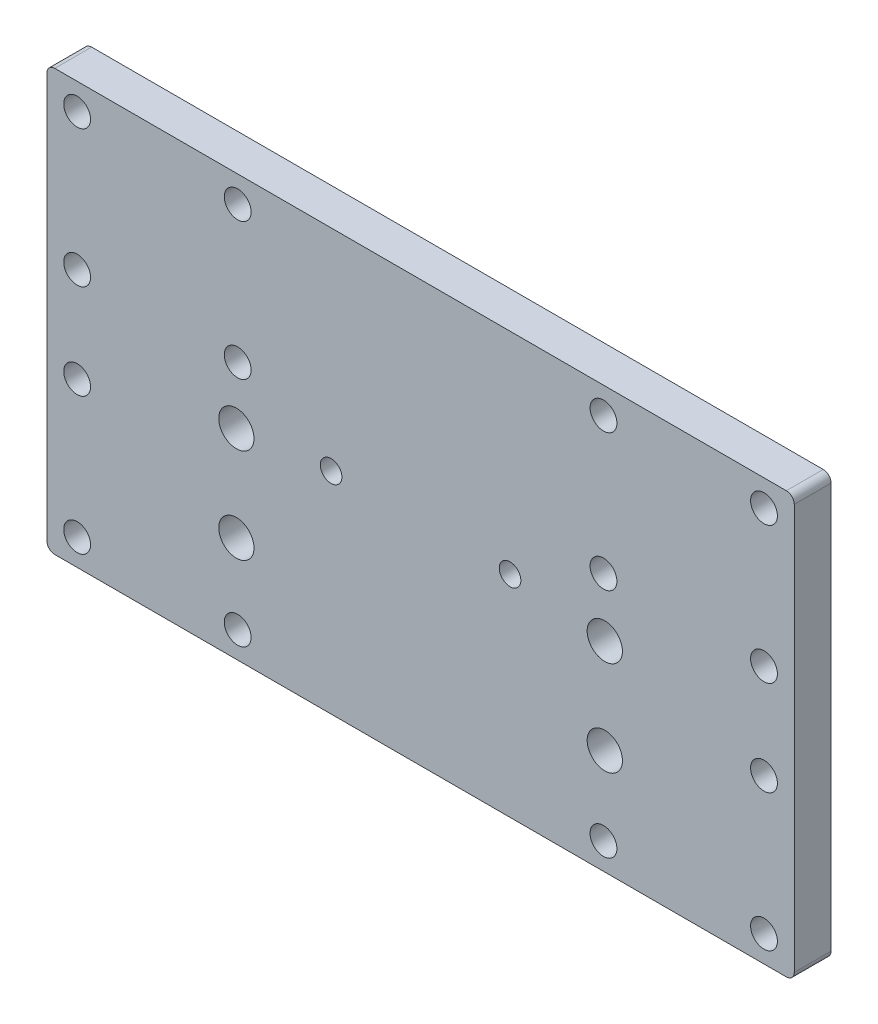
SolidWorks part; units mm, degrees
ref_plane "Front Plane" through (0, 0, 0) normal (0, 0, 1) x (1, 0, 0)
ref_plane "Top Plane" through (0, 0, 0) normal (0, 1, 0) x (1, 0, 0)
ref_plane "Right Plane" through (0, 0, 0) normal (1, 0, 0) x (0, 0, -1)
sketch "Sketch1" plane through (0, 0, 0) normal (0, 0, 1) x (1, 0, 0)
  line L1 (-71, -40) -> (71, -40)
  line L2 (-71, -40) -> (-71, 40)
  line L3 (-71, 40) -> (71, 40)
  line L4 (71, -40) -> (71, 40)
  line L5 (-71, -40) -> (71, 40) construction
  line L6 (-71, 40) -> (71, -40) construction
  point P0 (0, 0)
  dimension "D1" = 80
  dimension "D2" = 142
extrude "Boss-Extrude1" add sketch "Sketch1" along normal mid plane 7
sketch "Sketch2" plane through (0, 0, 3.5) normal (0, 0, 1) x (1, 0, 0)
  line L3 (-65.25, 40) -> (-65.25, -40)
  line L4 (-65.25, 40) -> (-65.25, -40) construction
  line L6 (65.25, -40) -> (65.25, 40)
  line L7 (65.25, -40) -> (65.25, 40) construction
  line L13 (-34.75, 40) -> (-34.75, -40)
  line L14 (-34.75, 40) -> (-34.75, -40) construction
  line L16 (34.75, -40) -> (34.75, 40)
  line L18 (34.75, -40) -> (34.75, 40) construction
  line L20 (71, 35) -> (-71, 35)
  line L21 (71, 35) -> (-71, 35) construction
  line L23 (-71, -35) -> (71, -35)
  line L24 (-71, -35) -> (71, -35) construction
  line L26 (71, 9) -> (-71, 9)
  line L27 (71, 9) -> (-71, 9) construction
  line L29 (-71, -9) -> (71, -9)
  line L30 (-71, -9) -> (71, -9) construction
  circle A0 centre (-65.25, 35) radius 2.55
  circle A1 centre (-34.75, 35) radius 2.55
  circle A2 centre (-34.75, 9) radius 2.55
  circle A3 centre (-65.25, 9) radius 2.55
  circle A4 centre (65.25, 35) radius 2.55
  circle A5 centre (65.25, 9) radius 2.55
  circle A6 centre (34.75, 9) radius 2.55
  circle A7 centre (34.75, 35) radius 2.55
  circle A8 centre (-65.25, -9) radius 2.55
  circle A10 centre (-34.75, -35) radius 2.55
  circle A11 centre (-65.25, -35) radius 2.55
  circle A13 centre (65.25, -9) radius 2.55
  circle A14 centre (65.25, -35) radius 2.55
  circle A15 centre (34.75, -35) radius 2.55
  dimension "D9" = 5.1
  dimension "D10" = 5.1
  dimension "D11" = 5.1
  dimension "D12" = 5.1
  dimension "D13" = 5.1
  dimension "D14" = 5.1
  dimension "D15" = 5.1
  dimension "D16" = 5.1
  dimension "D17" = 5.1
  dimension "D18" = 5.1
  dimension "D20" = 5.1
  dimension "D21" = 5.1
  dimension "D23" = 5.1
  dimension "D24" = 5.1
  dimension "D1" = 5.75
  dimension "D2" = 5.75
  dimension "D3" = 36.25
  dimension "D4" = 36.25
  dimension "D5" = 5
  dimension "D6" = 5
  dimension "D7" = 31
  dimension "D8" = 31
extrude "Cut-Extrude1" cut sketch "Sketch2" against normal through all
sketch "Sketch3" plane through (0, 0, 3.5) normal (0, 0, 1) x (1, 0, 0)
  line L0 (-71, -40) -> (71, -40) construction
  line L1 (-17, 0) -> (17, 0) construction
  line L7 (0, 40) -> (0, -40) construction
  line L8 (71, 40) -> (-71, 40) construction
  circle A0 centre (-17, 0) radius 2.05
  circle A3 centre (17, 0) radius 2.05
  point P0 (0, 0)
  dimension "D3" = 4.1
  dimension "D4" = 4.1
  dimension "D5" = 17
  dimension "D2" = 34
  dimension "D1" = 40
extrude "Cut-Extrude2" cut sketch "Sketch3" against normal through all
sketch "Sketch4" plane through (0, 0, 3.5) normal (0, 0, 1) x (1, 0, 0)
  line L0 (0, 40) -> (0, -40) construction
  line L1 (-35, -20) -> (35, -20) construction
  line L2 (-35, -20) -> (-35, -2) construction
  line L3 (-35, -2) -> (35, -2) construction
  line L4 (35, -20) -> (35, -2) construction
  line L5 (-35, -20) -> (35, -2) construction
  line L6 (-35, -2) -> (35, -20) construction
  line L7 (71, 40) -> (-71, 40) construction
  line L8 (-71, -40) -> (71, -40) construction
  circle A0 centre (-35, -2) radius 3.35
  circle A1 centre (35, -2) radius 3.35
  circle A2 centre (35, -20) radius 3.35
  circle A3 centre (-35, -20) radius 3.35
  point P0 (0, -11)
  dimension "D3" = 6.7
  dimension "D4" = 6.7
  dimension "D5" = 6.7
  dimension "D6" = 6.7
  dimension "D1" = 70
  dimension "D2" = 18
  dimension "D7" = 20
extrude "Cut-Extrude3" cut sketch "Sketch4" against normal through all
fillet "Fillet1" radius 1.5 4 edges at (-71, -40, 0) (71, -40, 0) (71, 40, 0) (-71, 40, 0)
equation "\"D4@Sketch3\"=\"D3@Sketch3\""
equation "\"D4@Sketch4\" = \"D3@Sketch4\""
equation "\"D5@Sketch4\"=\"D3@Sketch4\""
equation "\"D6@Sketch4\"=\"D3@Sketch4\""
equation "\"D10@Sketch2\"=\"D24@Sketch2\""
equation "\"D16@Sketch2\"=\"D24@Sketch2\""
